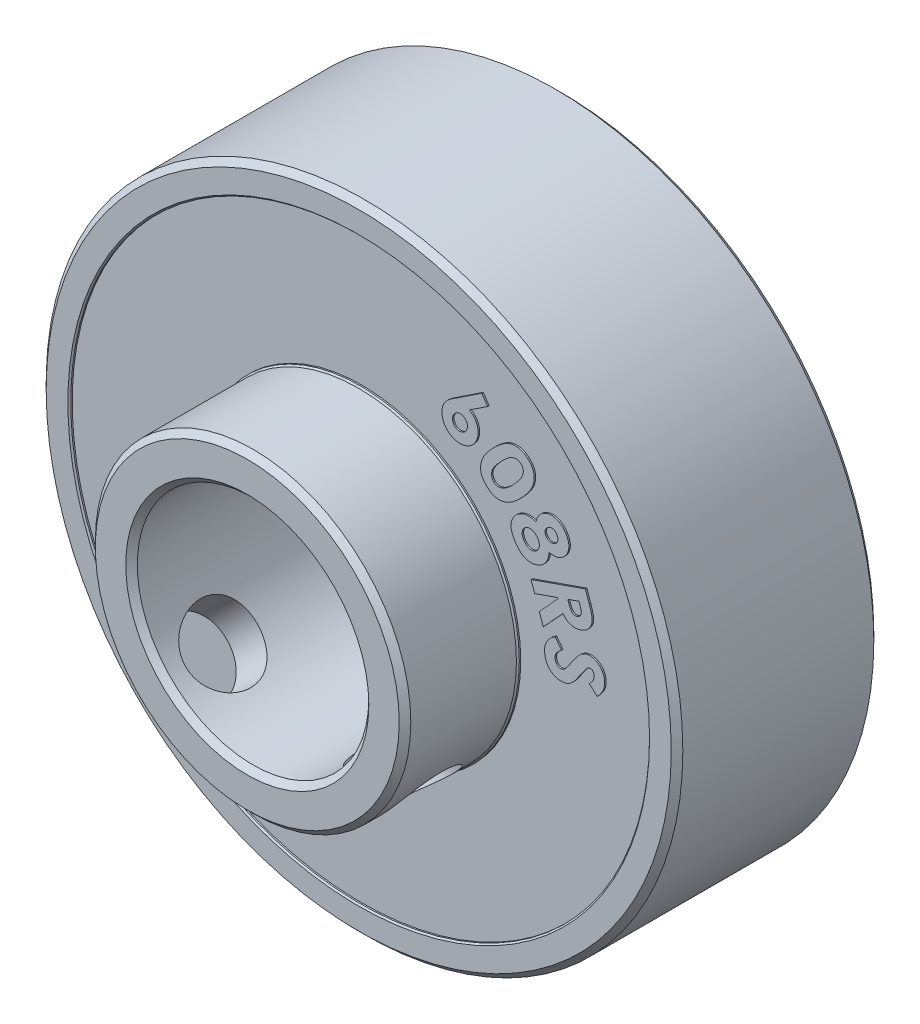
SolidWorks part; units mm, degrees
ref_plane "Front" through (0, 0, 0) normal (0, 0, 1) x (1, 0, 0)
ref_plane "Top" through (0, 0, 0) normal (0, 1, 0) x (1, 0, 0)
ref_plane "Right" through (0, 0, 0) normal (1, 0, 0) x (0, 0, -1)
sketch "Эскиз1" plane through (0, 0, 0) normal (0, 0, 1) x (1, 0, 0)
  circle A0 centre (0, 0) radius 4
  circle A1 centre (0, 0) radius 11
  dimension "D1" = 8
  dimension "D2" = 22
extrude "Бобышка-Вытянуть1" add sketch "Эскиз1" along normal blind 7
sketch "Эскиз2" plane through (0, 0, 7) normal (0, 0, 1) x (1, 0, 0)
  circle A0 centre (0, 0) radius 5.5
  circle A1 centre (0, 0) radius 10
  dimension "D1" = 11
  dimension "D2" = 20
extrude "Вырез-Вытянуть1" cut sketch "Эскиз2" against normal blind 0.1
extrude "Вырез-Вытянуть2" cut sketch "Эскиз2<2>" against normal blind 0.1 from offset 6.9 offset against normal yes
sketch "Эскиз2<2>" plane through (0, 0, 7) normal (0, 0, 1) x (1, 0, 0) same geometry as "Эскиз2"
chamfer "Фаска1" distance 0.05 angle 45 4 edges at (5.5, 0, 0) (5.5, 0, 7) (10, 0, 7) (10, 0, 0)
sketch "Эскиз3" plane through (0, 0, 7) normal (0, 0, 1) x (1, 0, 0)
  circle A0 centre (0, 0) radius 4
  circle A1 centre (0, 0) radius 5.45
extrude "Бобышка-Вытянуть2" add sketch "Эскиз3" along normal blind 3.85
sketch "Эскиз4" plane through (0, 0, 0.1) normal (0, 0, -1) x (-1, 0, 0)
  circle A0 centre (0, 0) radius 6.5 construction
  text T0 "<b>608RS</b>" font "Century Gothic" height 2
  dimension "D1" = 13
extrude "Бобышка-Вытянуть3" add sketch "Эскиз4" along normal blind 0.05
sketch "Эскиз6" plane through (0, 0, 6.9) normal (0, 0, 1) x (1, 0, 0)
  circle A0 centre (0, 0) radius 6.5 construction
  text T0 "<b>608RS</b>" font "Century Gothic" height 2
  dimension "D1" = 13
extrude "Бобышка-Вытянуть4" add sketch "Эскиз6" along normal blind 0.05
chamfer "Фаска2" distance 0.2 angle 45 5 edges at (4, 0, 0) (11, 0, 0) (4, 0, 10.85) (5.45, 0, 10.85) (11, 0, 7)
hole_wizard "Отверстие обработанное метчиком M31" positions "Трехмерный эскиз1" profile "Эскиз7" tap size "M3" standard "ISO"
sketch3d "Трехмерный эскиз1"
  line L3 (-3.9392, -3.7663, 8.85) -> (0, 0, 10.004)
  line L4 (0, 0, 10.004) -> (3.9392, -3.7663, 8.85)
  line L6 (0, 0, 10.65) -> (0, 0, 0.2) construction
  point P13 (-3.9392, -3.7663, 8.85)
  point P15 (3.9392, -3.7663, 8.85)
  dimension "D1" = 2
  dimension "D2" = 90
sketch "Эскиз7" plane through (-3.9392, -3.7663, 8.85) normal (0, 0, 1) x (0.6911, -0.7228, 0)
  line L0 (0, 0) -> (0, 5.7511)
  line L1 (0, 5.7511) -> (1.25, 5)
  line L2 (1.25, 5) -> (1.25, 0)
  line L5 (1.25, 0) -> (0, 0)
  line L10 (0, 5.7511) -> (-1.25, 5) construction
  line L11 (0, -6.35) -> (0, 107.95) construction
  dimension "Диаметр сверла" = 2.5
  dimension "Глубина сверла" = 5
  dimension "Угол заточки сверла" = 118
cosmetic thread "Условное изображение резьбы1" parameters "D1"=1.6503, "D2"=3
cosmetic thread "Условное изображение резьбы2" parameters "D1"=1.6503, "D2"=3
